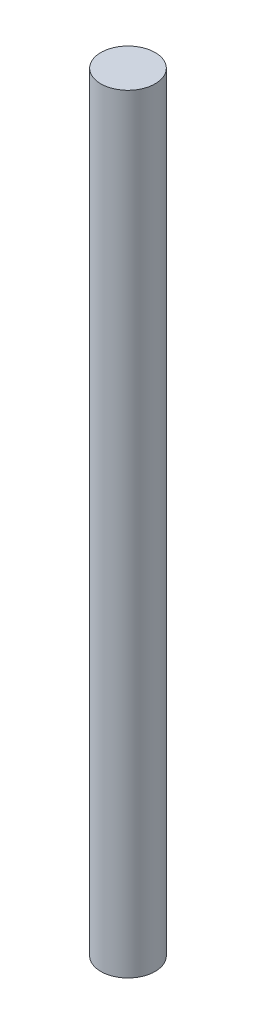
SolidWorks part; units mm, degrees
material "NON SPECIFIE"
ref_plane "Plan de face" through (0, 0, 0) normal (0, 0, 1) x (1, 0, 0)
ref_plane "Plan de dessus" through (0, 0, 0) normal (0, 1, 0) x (1, 0, 0)
ref_plane "Plan de droite" through (0, 0, 0) normal (1, 0, 0) x (0, 0, -1)
sketch "Sketch1" plane through (0, 0, 0) normal (0, 1, 0) x (1, 0, 0)
  circle A0 centre (0, 0) radius 6
  dimension "D1" = 12
extrude "Boss-Extrude1" add sketch "Sketch1" along normal blind 170
sketch "Sketch2" plane through (0, 170, 0) normal (0, 1, 0) x (1, 0, 0)
  circle A0 centre (0, 0) radius 19.5722
